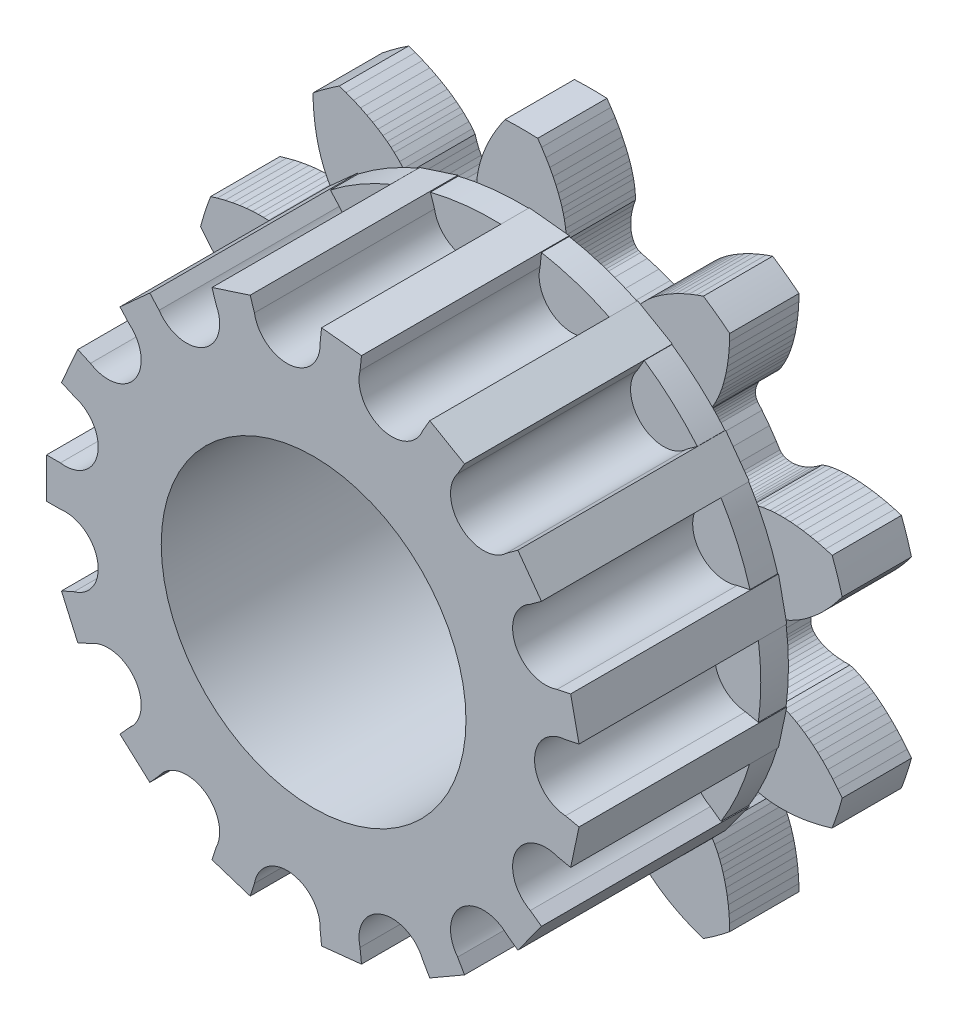
SolidWorks part; units mm, degrees
ref_plane "Front Plane" through (0, 0, 0) normal (0, 0, 1) x (1, 0, 0)
ref_plane "Top Plane" through (0, 0, 0) normal (0, 1, 0) x (1, 0, 0)
ref_plane "Right Plane" through (0, 0, 0) normal (1, 0, 0) x (0, 0, -1)
sketch "Model" plane through (0, 0, 0) normal (0, 0, 1) x (1, 0, 0)
  line L0 (44.9714, -18.1936) -> (45.0072, -17.6135)
  line L1 (45.0072, -17.6135) -> (45.064, -17.0676)
  line L2 (45.064, -17.0676) -> (45.1386, -16.5586)
  line L3 (45.1386, -16.5586) -> (45.2286, -16.0837)
  line L4 (45.2286, -16.0837) -> (45.3307, -15.6464)
  line L5 (45.3307, -15.6464) -> (45.4422, -15.245)
  line L6 (45.4422, -15.245) -> (45.5601, -14.8808)
  line L7 (45.5601, -14.8808) -> (45.6817, -14.5526)
  line L8 (45.6817, -14.5526) -> (45.8046, -14.2592)
  line L9 (45.8046, -14.2592) -> (46.0415, -13.7787)
  line L10 (46.0415, -13.7787) -> (46.2493, -13.433)
  line L11 (46.2493, -13.433) -> (46.4387, -13.1745)
  line L12 (46.4387, -13.1745) -> (46.7566, -12.9496)
  line L13 (46.7566, -12.9496) -> (47.0768, -12.6883)
  line L14 (47.0768, -12.6883) -> (47.3522, -12.4243)
  line L15 (47.3522, -12.4243) -> (47.5834, -12.1609)
  line L16 (47.5834, -12.1609) -> (47.7708, -11.9014)
  line L17 (47.7708, -11.9014) -> (47.9153, -11.6488)
  line L18 (47.9153, -11.6488) -> (48.0178, -11.4063)
  line L19 (48.0178, -11.4063) -> (48.0795, -11.177)
  line L20 (48.0795, -11.177) -> (48.1017, -10.9637)
  line L21 (48.1017, -10.9637) -> (48.086, -10.7695)
  line L22 (48.086, -10.7695) -> (48.034, -10.597)
  line L23 (48.034, -10.597) -> (47.9475, -10.4489)
  line L24 (47.9475, -10.4489) -> (47.6302, -10.0694)
  line L25 (47.6302, -10.0694) -> (47.0962, -9.3752)
  line L26 (47.0962, -9.3752) -> (46.601, -8.6528)
  line L27 (46.601, -8.6528) -> (46.3381, -8.2337)
  line L28 (46.3381, -8.2337) -> (46.224, -8.1057)
  line L29 (46.224, -8.1057) -> (46.076, -8.0029)
  line L30 (46.076, -8.0029) -> (45.8961, -7.9279)
  line L31 (45.8961, -7.9279) -> (45.6864, -7.8832)
  line L32 (45.6864, -7.8832) -> (45.4493, -7.871)
  line L33 (45.4493, -7.871) -> (45.187, -7.8936)
  line L34 (45.187, -7.8936) -> (44.9021, -7.9529)
  line L35 (44.9021, -7.9529) -> (44.5973, -8.051)
  line L36 (44.5973, -8.051) -> (44.2754, -8.1894)
  line L37 (44.2754, -8.1894) -> (43.9392, -8.3698)
  line L38 (43.9392, -8.3698) -> (43.5918, -8.5936)
  line L39 (43.5918, -8.5936) -> (43.2796, -8.8264)
  line L40 (43.2796, -8.8264) -> (42.9752, -8.9266)
  line L41 (42.9752, -8.9266) -> (42.5822, -9.0175)
  line L42 (42.5822, -9.0175) -> (42.052, -9.0943)
  line L43 (42.052, -9.0943) -> (41.735, -9.1205)
  line L44 (41.735, -9.1205) -> (41.3854, -9.1348)
  line L45 (41.3854, -9.1348) -> (41.0026, -9.1343)
  line L46 (41.0026, -9.1343) -> (40.5863, -9.1164)
  line L47 (40.5863, -9.1164) -> (40.1389, -9.0783)
  line L48 (40.1389, -9.0783) -> (39.6594, -9.0172)
  line L49 (39.6594, -9.0172) -> (39.1523, -8.9308)
  line L50 (39.1523, -8.9308) -> (38.6155, -8.8161)
  line L51 (38.6155, -8.8161) -> (38.0528, -8.671)
  line L52 (38.0528, -8.671) -> (37.565, -8.5243)
  line L53 (36.8392, -6.2906) -> (37.1476, -5.8853)
  line L54 (37.1476, -5.8853) -> (37.5176, -5.4371)
  line L55 (37.5176, -5.4371) -> (37.8845, -5.0288)
  line L56 (37.8845, -5.0288) -> (38.244, -4.6608)
  line L57 (38.244, -4.6608) -> (38.596, -4.3295)
  line L58 (38.596, -4.3295) -> (38.9355, -4.0358)
  line L59 (38.9355, -4.0358) -> (39.2618, -3.7766)
  line L60 (39.2618, -3.7766) -> (39.5712, -3.5512)
  line L61 (39.5712, -3.5512) -> (39.8624, -3.3572)
  line L62 (39.8624, -3.3572) -> (40.1343, -3.1921)
  line L63 (40.1343, -3.1921) -> (40.6084, -2.9426)
  line L64 (40.6084, -2.9426) -> (40.9797, -2.7851)
  line L65 (40.9797, -2.7851) -> (41.2849, -2.6873)
  line L66 (41.2849, -2.6873) -> (41.6743, -2.6921)
  line L67 (41.6743, -2.6921) -> (42.0869, -2.669)
  line L68 (42.0869, -2.669) -> (42.4649, -2.6173)
  line L69 (42.4649, -2.6173) -> (42.8067, -2.5401)
  line L70 (42.8067, -2.5401) -> (43.1109, -2.4403)
  line L71 (43.1109, -2.4403) -> (43.3763, -2.3209)
  line L72 (43.3763, -2.3209) -> (43.6018, -2.1849)
  line L73 (43.6018, -2.1849) -> (43.7865, -2.0357)
  line L74 (43.7865, -2.0357) -> (43.9298, -1.8762)
  line L75 (43.9298, -1.8762) -> (44.0312, -1.7098)
  line L76 (44.0312, -1.7098) -> (44.0905, -1.5397)
  line L77 (44.0905, -1.5397) -> (44.1076, -1.369)
  line L78 (44.1076, -1.369) -> (44.074, -0.8755)
  line L79 (44.074, -0.8755) -> (44.05, 0)
  line L80 (44.05, 0) -> (44.074, 0.8755)
  line L81 (44.074, 0.8755) -> (44.1076, 1.369)
  line L82 (44.1076, 1.369) -> (44.0905, 1.5397)
  line L83 (44.0905, 1.5397) -> (44.0312, 1.7098)
  line L84 (44.0312, 1.7098) -> (43.9298, 1.8762)
  line L85 (43.9298, 1.8762) -> (43.7865, 2.0357)
  line L86 (43.7865, 2.0357) -> (43.6018, 2.1849)
  line L87 (43.6018, 2.1849) -> (43.3763, 2.3209)
  line L88 (43.3763, 2.3209) -> (43.1109, 2.4403)
  line L89 (43.1109, 2.4403) -> (42.8067, 2.5401)
  line L90 (42.8067, 2.5401) -> (42.4649, 2.6173)
  line L91 (42.4649, 2.6173) -> (42.0869, 2.669)
  line L92 (42.0869, 2.669) -> (41.6743, 2.6921)
  line L93 (41.6743, 2.6921) -> (41.2849, 2.6873)
  line L94 (41.2849, 2.6873) -> (40.9797, 2.7851)
  line L95 (40.9797, 2.7851) -> (40.6084, 2.9426)
  line L96 (40.6084, 2.9426) -> (40.1343, 3.1921)
  line L97 (40.1343, 3.1921) -> (39.8624, 3.3572)
  line L98 (39.8624, 3.3572) -> (39.5712, 3.5512)
  line L99 (39.5712, 3.5512) -> (39.2618, 3.7766)
  line L100 (39.2618, 3.7766) -> (38.9355, 4.0358)
  line L101 (38.9355, 4.0358) -> (38.596, 4.3295)
  line L102 (38.596, 4.3295) -> (38.244, 4.6608)
  line L103 (38.244, 4.6608) -> (37.8845, 5.0288)
  line L104 (37.8845, 5.0288) -> (37.5176, 5.4371)
  line L105 (37.5176, 5.4371) -> (37.1476, 5.8853)
  line L106 (37.1476, 5.8853) -> (36.8392, 6.2906)
  line L107 (37.565, 8.5243) -> (38.0528, 8.671)
  line L108 (38.0528, 8.671) -> (38.6155, 8.8161)
  line L109 (38.6155, 8.8161) -> (39.1523, 8.9308)
  line L110 (39.1523, 8.9308) -> (39.6594, 9.0172)
  line L111 (39.6594, 9.0172) -> (40.1389, 9.0783)
  line L112 (40.1389, 9.0783) -> (40.5863, 9.1164)
  line L113 (40.5863, 9.1164) -> (41.0026, 9.1343)
  line L114 (41.0026, 9.1343) -> (41.3854, 9.1348)
  line L115 (41.3854, 9.1348) -> (41.735, 9.1205)
  line L116 (41.735, 9.1205) -> (42.052, 9.0943)
  line L117 (42.052, 9.0943) -> (42.5822, 9.0175)
  line L118 (42.5822, 9.0175) -> (42.9752, 8.9266)
  line L119 (42.9752, 8.9266) -> (43.2796, 8.8264)
  line L120 (43.2796, 8.8264) -> (43.5918, 8.5936)
  line L121 (43.5918, 8.5936) -> (43.9392, 8.3698)
  line L122 (43.9392, 8.3698) -> (44.2754, 8.1894)
  line L123 (44.2754, 8.1894) -> (44.5973, 8.051)
  line L124 (44.5973, 8.051) -> (44.9021, 7.9529)
  line L125 (44.9021, 7.9529) -> (45.187, 7.8936)
  line L126 (45.187, 7.8936) -> (45.4493, 7.871)
  line L127 (45.4493, 7.871) -> (45.6864, 7.8832)
  line L128 (45.6864, 7.8832) -> (45.8961, 7.9279)
  line L129 (45.8961, 7.9279) -> (46.076, 8.0029)
  line L130 (46.076, 8.0029) -> (46.224, 8.1057)
  line L131 (46.224, 8.1057) -> (46.3381, 8.2337)
  line L132 (46.3381, 8.2337) -> (46.601, 8.6528)
  line L133 (46.601, 8.6528) -> (47.0962, 9.3752)
  line L134 (47.0962, 9.3752) -> (47.6302, 10.0694)
  line L135 (47.6302, 10.0694) -> (47.9475, 10.4489)
  line L136 (47.9475, 10.4489) -> (48.034, 10.597)
  line L137 (48.034, 10.597) -> (48.086, 10.7695)
  line L138 (48.086, 10.7695) -> (48.1017, 10.9637)
  line L139 (48.1017, 10.9637) -> (48.0795, 11.177)
  line L140 (48.0795, 11.177) -> (48.0178, 11.4063)
  line L141 (48.0178, 11.4063) -> (47.9153, 11.6488)
  line L142 (47.9153, 11.6488) -> (47.7708, 11.9014)
  line L143 (47.7708, 11.9014) -> (47.5834, 12.1609)
  line L144 (47.5834, 12.1609) -> (47.3522, 12.4243)
  line L145 (47.3522, 12.4243) -> (47.0768, 12.6883)
  line L146 (47.0768, 12.6883) -> (46.7566, 12.9496)
  line L147 (46.7566, 12.9496) -> (46.4387, 13.1745)
  line L148 (46.4387, 13.1745) -> (46.2493, 13.433)
  line L149 (46.2493, 13.433) -> (46.0415, 13.7787)
  line L150 (46.0415, 13.7787) -> (45.8046, 14.2592)
  line L151 (45.8046, 14.2592) -> (45.6817, 14.5526)
  line L152 (45.6817, 14.5526) -> (45.5601, 14.8808)
  line L153 (45.5601, 14.8808) -> (45.4422, 15.245)
  line L154 (45.4422, 15.245) -> (45.3307, 15.6464)
  line L155 (45.3307, 15.6464) -> (45.2286, 16.0837)
  line L156 (45.2286, 16.0837) -> (45.1386, 16.5586)
  line L157 (45.1386, 16.5586) -> (45.064, 17.0676)
  line L158 (45.064, 17.0676) -> (45.0072, 17.6135)
  line L159 (45.0072, 17.6135) -> (44.9714, 18.1936)
  line L160 (44.9714, 18.1936) -> (44.9601, 18.7028)
  line L161 (46.8602, 20.0833) -> (47.341, 19.9152)
  line L162 (47.341, 19.9152) -> (47.8816, 19.7019)
  line L163 (47.8816, 19.7019) -> (48.3833, 19.4792)
  line L164 (48.3833, 19.4792) -> (48.8443, 19.2509)
  line L165 (48.8443, 19.2509) -> (49.2681, 19.0186)
  line L166 (49.2681, 19.0186) -> (49.6525, 18.7864)
  line L167 (49.6525, 18.7864) -> (49.9998, 18.5562)
  line L168 (49.9998, 18.5562) -> (50.3097, 18.3316)
  line L169 (50.3097, 18.3316) -> (50.5842, 18.1146)
  line L170 (50.5842, 18.1146) -> (50.8253, 17.907)
  line L171 (50.8253, 17.907) -> (51.2091, 17.5332)
  line L172 (51.2091, 17.5332) -> (51.4736, 17.2287)
  line L173 (51.4736, 17.2287) -> (51.6609, 16.9687)
  line L174 (51.6609, 16.9687) -> (51.7767, 16.5968)
  line L175 (51.7767, 16.5968) -> (51.9262, 16.2116)
  line L176 (51.9262, 16.2116) -> (52.0921, 15.8681)
  line L177 (52.0921, 15.8681) -> (52.2712, 15.5668)
  line L178 (52.2712, 15.5668) -> (52.4601, 15.3084)
  line L179 (52.4601, 15.3084) -> (52.6557, 15.0929)
  line L180 (52.6557, 15.0929) -> (52.8547, 14.9205)
  line L181 (52.8547, 14.9205) -> (53.0537, 14.7909)
  line L182 (53.0537, 14.7909) -> (53.2496, 14.7039)
  line L183 (53.2496, 14.7039) -> (53.4392, 14.6588)
  line L184 (53.4392, 14.6588) -> (53.6194, 14.655)
  line L185 (53.6194, 14.655) -> (53.7869, 14.6915)
  line L186 (53.7869, 14.6915) -> (54.2459, 14.876)
  line L187 (54.2459, 14.876) -> (55.0712, 15.1694)
  line L188 (55.0712, 15.1694) -> (55.9113, 15.4171)
  line L189 (55.9113, 15.4171) -> (56.391, 15.5376)
  line L190 (56.391, 15.5376) -> (56.548, 15.6066)
  line L191 (56.548, 15.6066) -> (56.6915, 15.7156)
  line L192 (56.6915, 15.7156) -> (56.8184, 15.8635)
  line L193 (56.8184, 15.8635) -> (56.9258, 16.049)
  line L194 (56.9258, 16.049) -> (57.0107, 16.2708)
  line L195 (57.0107, 16.2708) -> (57.0703, 16.5273)
  line L196 (57.0703, 16.5273) -> (57.1018, 16.8165)
  line L197 (57.1018, 16.8165) -> (57.1028, 17.1367)
  line L198 (57.1028, 17.1367) -> (57.0706, 17.4857)
  line L199 (57.0706, 17.4857) -> (57.0029, 17.8611)
  line L200 (57.0029, 17.8611) -> (56.8974, 18.2607)
  line L201 (56.8974, 18.2607) -> (56.7725, 18.6296)
  line L202 (56.7725, 18.6296) -> (56.7712, 18.95)
  line L203 (56.7712, 18.95) -> (56.8063, 19.3518)
  line L204 (56.8063, 19.3518) -> (56.897, 19.8798)
  line L205 (56.897, 19.8798) -> (56.97, 20.1894)
  line L206 (56.97, 20.1894) -> (57.0646, 20.5264)
  line L207 (57.0646, 20.5264) -> (57.1833, 20.8903)
  line L208 (57.1833, 20.8903) -> (57.329, 21.2806)
  line L209 (57.329, 21.2806) -> (57.5034, 21.6944)
  line L210 (57.5034, 21.6944) -> (57.7097, 22.1315)
  line L211 (57.7097, 22.1315) -> (57.9486, 22.5871)
  line L212 (57.9486, 22.5871) -> (58.2236, 23.0622)
  line L213 (58.2236, 23.0622) -> (58.5355, 23.5525)
  line L214 (58.5355, 23.5525) -> (58.8257, 23.9711)
  line L215 (61.1743, 23.9711) -> (61.4645, 23.5525)
  line L216 (61.4645, 23.5525) -> (61.7764, 23.0622)
  line L217 (61.7764, 23.0622) -> (62.0514, 22.5871)
  line L218 (62.0514, 22.5871) -> (62.2903, 22.1315)
  line L219 (62.2903, 22.1315) -> (62.4966, 21.6944)
  line L220 (62.4966, 21.6944) -> (62.671, 21.2806)
  line L221 (62.671, 21.2806) -> (62.8167, 20.8903)
  line L222 (62.8167, 20.8903) -> (62.9354, 20.5264)
  line L223 (62.9354, 20.5264) -> (63.03, 20.1894)
  line L224 (63.03, 20.1894) -> (63.103, 19.8798)
  line L225 (63.103, 19.8798) -> (63.1937, 19.3518)
  line L226 (63.1937, 19.3518) -> (63.2288, 18.95)
  line L227 (63.2288, 18.95) -> (63.2275, 18.6296)
  line L228 (63.2275, 18.6296) -> (63.1026, 18.2607)
  line L229 (63.1026, 18.2607) -> (62.9971, 17.8611)
  line L230 (62.9971, 17.8611) -> (62.9294, 17.4857)
  line L231 (62.9294, 17.4857) -> (62.8972, 17.1367)
  line L232 (62.8972, 17.1367) -> (62.8982, 16.8165)
  line L233 (62.8982, 16.8165) -> (62.9297, 16.5273)
  line L234 (62.9297, 16.5273) -> (62.9893, 16.2708)
  line L235 (62.9893, 16.2708) -> (63.0742, 16.049)
  line L236 (63.0742, 16.049) -> (63.1816, 15.8635)
  line L237 (63.1816, 15.8635) -> (63.3085, 15.7156)
  line L238 (63.3085, 15.7156) -> (63.452, 15.6066)
  line L239 (63.452, 15.6066) -> (63.609, 15.5376)
  line L240 (63.609, 15.5376) -> (64.0887, 15.4171)
  line L241 (64.0887, 15.4171) -> (64.9288, 15.1694)
  line L242 (64.9288, 15.1694) -> (65.7541, 14.876)
  line L243 (65.7541, 14.876) -> (66.2131, 14.6915)
  line L244 (66.2131, 14.6915) -> (66.3806, 14.655)
  line L245 (66.3806, 14.655) -> (66.5608, 14.6588)
  line L246 (66.5608, 14.6588) -> (66.7504, 14.7039)
  line L247 (66.7504, 14.7039) -> (66.9463, 14.7909)
  line L248 (66.9463, 14.7909) -> (67.1453, 14.9205)
  line L249 (67.1453, 14.9205) -> (67.3443, 15.0929)
  line L250 (67.3443, 15.0929) -> (67.5399, 15.3084)
  line L251 (67.5399, 15.3084) -> (67.7288, 15.5668)
  line L252 (67.7288, 15.5668) -> (67.9079, 15.8681)
  line L253 (67.9079, 15.8681) -> (68.0738, 16.2116)
  line L254 (68.0738, 16.2116) -> (68.2233, 16.5968)
  line L255 (68.2233, 16.5968) -> (68.3391, 16.9687)
  line L256 (68.3391, 16.9687) -> (68.5264, 17.2287)
  line L257 (68.5264, 17.2287) -> (68.7909, 17.5332)
  line L258 (68.7909, 17.5332) -> (69.1747, 17.907)
  line L259 (69.1747, 17.907) -> (69.4158, 18.1146)
  line L260 (69.4158, 18.1146) -> (69.6903, 18.3316)
  line L261 (69.6903, 18.3316) -> (70.0002, 18.5562)
  line L262 (70.0002, 18.5562) -> (70.3475, 18.7864)
  line L263 (70.3475, 18.7864) -> (70.7319, 19.0186)
  line L264 (70.7319, 19.0186) -> (71.1557, 19.2509)
  line L265 (71.1557, 19.2509) -> (71.6167, 19.4792)
  line L266 (71.6167, 19.4792) -> (72.1184, 19.7019)
  line L267 (72.1184, 19.7019) -> (72.659, 19.9152)
  line L268 (72.659, 19.9152) -> (73.1398, 20.0833)
  line L269 (75.0399, 18.7028) -> (75.0286, 18.1936)
  line L270 (75.0286, 18.1936) -> (74.9928, 17.6135)
  line L271 (74.9928, 17.6135) -> (74.936, 17.0676)
  line L272 (74.936, 17.0676) -> (74.8614, 16.5586)
  line L273 (74.8614, 16.5586) -> (74.7714, 16.0837)
  line L274 (74.7714, 16.0837) -> (74.6693, 15.6464)
  line L275 (74.6693, 15.6464) -> (74.5578, 15.245)
  line L276 (74.5578, 15.245) -> (74.4399, 14.8808)
  line L277 (74.4399, 14.8808) -> (74.3183, 14.5526)
  line L278 (74.3183, 14.5526) -> (74.1954, 14.2592)
  line L279 (74.1954, 14.2592) -> (73.9585, 13.7787)
  line L280 (73.9585, 13.7787) -> (73.7507, 13.433)
  line L281 (73.7507, 13.433) -> (73.5613, 13.1745)
  line L282 (73.5613, 13.1745) -> (73.2434, 12.9496)
  line L283 (73.2434, 12.9496) -> (72.9232, 12.6883)
  line L284 (72.9232, 12.6883) -> (72.6478, 12.4243)
  line L285 (72.6478, 12.4243) -> (72.4166, 12.1609)
  line L286 (72.4166, 12.1609) -> (72.2292, 11.9014)
  line L287 (72.2292, 11.9014) -> (72.0847, 11.6488)
  line L288 (72.0847, 11.6488) -> (71.9822, 11.4063)
  line L289 (71.9822, 11.4063) -> (71.9205, 11.177)
  line L290 (71.9205, 11.177) -> (71.8983, 10.9637)
  line L291 (71.8983, 10.9637) -> (71.914, 10.7695)
  line L292 (71.914, 10.7695) -> (71.966, 10.597)
  line L293 (71.966, 10.597) -> (72.0525, 10.4489)
  line L294 (72.0525, 10.4489) -> (72.3698, 10.0694)
  line L295 (72.3698, 10.0694) -> (72.9038, 9.3752)
  line L296 (72.9038, 9.3752) -> (73.399, 8.6528)
  line L297 (73.399, 8.6528) -> (73.6619, 8.2337)
  line L298 (73.6619, 8.2337) -> (73.776, 8.1057)
  line L299 (73.776, 8.1057) -> (73.924, 8.0029)
  line L300 (73.924, 8.0029) -> (74.1039, 7.9279)
  line L301 (74.1039, 7.9279) -> (74.3136, 7.8832)
  line L302 (74.3136, 7.8832) -> (74.5507, 7.871)
  line L303 (74.5507, 7.871) -> (74.813, 7.8936)
  line L304 (74.813, 7.8936) -> (75.0979, 7.9529)
  line L305 (75.0979, 7.9529) -> (75.4027, 8.051)
  line L306 (75.4027, 8.051) -> (75.7246, 8.1894)
  line L307 (75.7246, 8.1894) -> (76.0608, 8.3698)
  line L308 (76.0608, 8.3698) -> (76.4082, 8.5936)
  line L309 (76.4082, 8.5936) -> (76.7204, 8.8264)
  line L310 (76.7204, 8.8264) -> (77.0248, 8.9266)
  line L311 (77.0248, 8.9266) -> (77.4178, 9.0175)
  line L312 (77.4178, 9.0175) -> (77.948, 9.0943)
  line L313 (77.948, 9.0943) -> (78.265, 9.1205)
  line L314 (78.265, 9.1205) -> (78.6146, 9.1348)
  line L315 (78.6146, 9.1348) -> (78.9974, 9.1343)
  line L316 (78.9974, 9.1343) -> (79.4137, 9.1164)
  line L317 (79.4137, 9.1164) -> (79.8611, 9.0783)
  line L318 (79.8611, 9.0783) -> (80.3406, 9.0172)
  line L319 (80.3406, 9.0172) -> (80.8477, 8.9308)
  line L320 (80.8477, 8.9308) -> (81.3845, 8.8161)
  line L321 (81.3845, 8.8161) -> (81.9472, 8.671)
  line L322 (81.9472, 8.671) -> (82.435, 8.5243)
  line L323 (83.1608, 6.2906) -> (82.8524, 5.8853)
  line L324 (82.8524, 5.8853) -> (82.4824, 5.4371)
  line L325 (82.4824, 5.4371) -> (82.1155, 5.0288)
  line L326 (82.1155, 5.0288) -> (81.756, 4.6608)
  line L327 (81.756, 4.6608) -> (81.4041, 4.3295)
  line L328 (81.4041, 4.3295) -> (81.0645, 4.0358)
  line L329 (81.0645, 4.0358) -> (80.7382, 3.7766)
  line L330 (80.7382, 3.7766) -> (80.4288, 3.5512)
  line L331 (80.4288, 3.5512) -> (80.1376, 3.3572)
  line L332 (80.1376, 3.3572) -> (79.8657, 3.1921)
  line L333 (79.8657, 3.1921) -> (79.3916, 2.9426)
  line L334 (79.3916, 2.9426) -> (79.0203, 2.7851)
  line L335 (79.0203, 2.7851) -> (78.7151, 2.6873)
  line L336 (78.7151, 2.6873) -> (78.3257, 2.6921)
  line L337 (78.3257, 2.6921) -> (77.9131, 2.669)
  line L338 (77.9131, 2.669) -> (77.5351, 2.6173)
  line L339 (77.5351, 2.6173) -> (77.1933, 2.5401)
  line L340 (77.1933, 2.5401) -> (76.8891, 2.4403)
  line L341 (76.8891, 2.4403) -> (76.6237, 2.3209)
  line L342 (76.6237, 2.3209) -> (76.3983, 2.1849)
  line L343 (76.3983, 2.1849) -> (76.2135, 2.0357)
  line L344 (76.2135, 2.0357) -> (76.0702, 1.8762)
  line L345 (76.0702, 1.8762) -> (75.9688, 1.7098)
  line L346 (75.9688, 1.7098) -> (75.9095, 1.5397)
  line L347 (75.9095, 1.5397) -> (75.8924, 1.369)
  line L348 (75.8924, 1.369) -> (75.926, 0.8755)
  line L349 (75.926, 0.8755) -> (75.95, 0)
  line L350 (75.95, 0) -> (75.926, -0.8755)
  line L351 (75.926, -0.8755) -> (75.8924, -1.369)
  line L352 (75.8924, -1.369) -> (75.9095, -1.5397)
  line L353 (75.9095, -1.5397) -> (75.9688, -1.7098)
  line L354 (75.9688, -1.7098) -> (76.0702, -1.8762)
  line L355 (76.0702, -1.8762) -> (76.2135, -2.0357)
  line L356 (76.2135, -2.0357) -> (76.3983, -2.1849)
  line L357 (76.3983, -2.1849) -> (76.6237, -2.3209)
  line L358 (76.6237, -2.3209) -> (76.8891, -2.4403)
  line L359 (76.8891, -2.4403) -> (77.1933, -2.5401)
  line L360 (77.1933, -2.5401) -> (77.5351, -2.6173)
  line L361 (77.5351, -2.6173) -> (77.9131, -2.669)
  line L362 (77.9131, -2.669) -> (78.3257, -2.6921)
  line L363 (78.3257, -2.6921) -> (78.7151, -2.6873)
  line L364 (78.7151, -2.6873) -> (79.0203, -2.7851)
  line L365 (79.0203, -2.7851) -> (79.3916, -2.9426)
  line L366 (79.3916, -2.9426) -> (79.8657, -3.1921)
  line L367 (79.8657, -3.1921) -> (80.1376, -3.3572)
  line L368 (80.1376, -3.3572) -> (80.4288, -3.5512)
  line L369 (80.4288, -3.5512) -> (80.7382, -3.7766)
  line L370 (80.7382, -3.7766) -> (81.0645, -4.0358)
  line L371 (81.0645, -4.0358) -> (81.4041, -4.3295)
  line L372 (81.4041, -4.3295) -> (81.756, -4.6608)
  line L373 (81.756, -4.6608) -> (82.1155, -5.0288)
  line L374 (82.1155, -5.0288) -> (82.4824, -5.4371)
  line L375 (82.4824, -5.4371) -> (82.8524, -5.8853)
  line L376 (82.8524, -5.8853) -> (83.1608, -6.2906)
  line L377 (82.435, -8.5243) -> (81.9472, -8.671)
  line L378 (81.9472, -8.671) -> (81.3845, -8.8161)
  line L379 (81.3845, -8.8161) -> (80.8477, -8.9308)
  line L380 (80.8477, -8.9308) -> (80.3406, -9.0172)
  line L381 (80.3406, -9.0172) -> (79.8611, -9.0783)
  line L382 (79.8611, -9.0783) -> (79.4137, -9.1164)
  line L383 (79.4137, -9.1164) -> (78.9974, -9.1343)
  line L384 (78.9974, -9.1343) -> (78.6146, -9.1348)
  line L385 (78.6146, -9.1348) -> (78.265, -9.1205)
  line L386 (78.265, -9.1205) -> (77.948, -9.0943)
  line L387 (77.948, -9.0943) -> (77.4178, -9.0175)
  line L388 (77.4178, -9.0175) -> (77.0248, -8.9266)
  line L389 (77.0248, -8.9266) -> (76.7204, -8.8264)
  line L390 (76.7204, -8.8264) -> (76.4082, -8.5936)
  line L391 (76.4082, -8.5936) -> (76.0608, -8.3698)
  line L392 (76.0608, -8.3698) -> (75.7246, -8.1894)
  line L393 (75.7246, -8.1894) -> (75.4027, -8.051)
  line L394 (75.4027, -8.051) -> (75.0979, -7.9529)
  line L395 (75.0979, -7.9529) -> (74.813, -7.8936)
  line L396 (74.813, -7.8936) -> (74.5507, -7.871)
  line L397 (74.5507, -7.871) -> (74.3136, -7.8832)
  line L398 (74.3136, -7.8832) -> (74.1039, -7.9279)
  line L399 (74.1039, -7.9279) -> (73.924, -8.0029)
  line L400 (73.924, -8.0029) -> (73.776, -8.1057)
  line L401 (73.776, -8.1057) -> (73.6619, -8.2337)
  line L402 (73.6619, -8.2337) -> (73.399, -8.6528)
  line L403 (73.399, -8.6528) -> (72.9038, -9.3752)
  line L404 (72.9038, -9.3752) -> (72.3698, -10.0694)
  line L405 (72.3698, -10.0694) -> (72.0525, -10.4489)
  line L406 (72.0525, -10.4489) -> (71.966, -10.597)
  line L407 (71.966, -10.597) -> (71.914, -10.7695)
  line L408 (71.914, -10.7695) -> (71.8983, -10.9637)
  line L409 (71.8983, -10.9637) -> (71.9205, -11.177)
  line L410 (71.9205, -11.177) -> (71.9822, -11.4063)
  line L411 (71.9822, -11.4063) -> (72.0847, -11.6488)
  line L412 (72.0847, -11.6488) -> (72.2292, -11.9014)
  line L413 (72.2292, -11.9014) -> (72.4166, -12.1609)
  line L414 (72.4166, -12.1609) -> (72.6478, -12.4243)
  line L415 (72.6478, -12.4243) -> (72.9232, -12.6883)
  line L416 (72.9232, -12.6883) -> (73.2434, -12.9496)
  line L417 (73.2434, -12.9496) -> (73.5613, -13.1745)
  line L418 (73.5613, -13.1745) -> (73.7507, -13.433)
  line L419 (73.7507, -13.433) -> (73.9585, -13.7787)
  line L420 (73.9585, -13.7787) -> (74.1954, -14.2592)
  line L421 (74.1954, -14.2592) -> (74.3183, -14.5526)
  line L422 (74.3183, -14.5526) -> (74.4399, -14.8808)
  line L423 (74.4399, -14.8808) -> (74.5578, -15.245)
  line L424 (74.5578, -15.245) -> (74.6693, -15.6464)
  line L425 (74.6693, -15.6464) -> (74.7714, -16.0837)
  line L426 (74.7714, -16.0837) -> (74.8614, -16.5586)
  line L427 (74.8614, -16.5586) -> (74.936, -17.0676)
  line L428 (74.936, -17.0676) -> (74.9928, -17.6135)
  line L429 (74.9928, -17.6135) -> (75.0286, -18.1936)
  line L430 (75.0286, -18.1936) -> (75.0399, -18.7028)
  line L431 (73.1398, -20.0833) -> (72.659, -19.9152)
  line L432 (72.659, -19.9152) -> (72.1184, -19.7019)
  line L433 (72.1184, -19.7019) -> (71.6167, -19.4792)
  line L434 (71.6167, -19.4792) -> (71.1557, -19.2509)
  line L435 (71.1557, -19.2509) -> (70.7319, -19.0186)
  line L436 (70.7319, -19.0186) -> (70.3475, -18.7864)
  line L437 (70.3475, -18.7864) -> (70.0002, -18.5562)
  line L438 (70.0002, -18.5562) -> (69.6903, -18.3316)
  line L439 (69.6903, -18.3316) -> (69.4158, -18.1146)
  line L440 (69.4158, -18.1146) -> (69.1747, -17.907)
  line L441 (69.1747, -17.907) -> (68.7909, -17.5332)
  line L442 (68.7909, -17.5332) -> (68.5264, -17.2287)
  line L443 (68.5264, -17.2287) -> (68.3391, -16.9687)
  line L444 (68.3391, -16.9687) -> (68.2233, -16.5968)
  line L445 (68.2233, -16.5968) -> (68.0738, -16.2116)
  line L446 (68.0738, -16.2116) -> (67.9079, -15.8681)
  line L447 (67.9079, -15.8681) -> (67.7288, -15.5668)
  line L448 (67.7288, -15.5668) -> (67.5399, -15.3084)
  line L449 (67.5399, -15.3084) -> (67.3443, -15.0929)
  line L450 (67.3443, -15.0929) -> (67.1453, -14.9205)
  line L451 (67.1453, -14.9205) -> (66.9463, -14.7909)
  line L452 (66.9463, -14.7909) -> (66.7504, -14.7039)
  line L453 (66.7504, -14.7039) -> (66.5608, -14.6588)
  line L454 (66.5608, -14.6588) -> (66.3806, -14.655)
  line L455 (66.3806, -14.655) -> (66.2131, -14.6915)
  line L456 (66.2131, -14.6915) -> (65.7541, -14.876)
  line L457 (65.7541, -14.876) -> (64.9288, -15.1694)
  line L458 (64.9288, -15.1694) -> (64.0887, -15.4171)
  line L459 (64.0887, -15.4171) -> (63.609, -15.5376)
  line L460 (63.609, -15.5376) -> (63.452, -15.6066)
  line L461 (63.452, -15.6066) -> (63.3085, -15.7156)
  line L462 (63.3085, -15.7156) -> (63.1816, -15.8635)
  line L463 (63.1816, -15.8635) -> (63.0742, -16.049)
  line L464 (63.0742, -16.049) -> (62.9893, -16.2708)
  line L465 (62.9893, -16.2708) -> (62.9297, -16.5273)
  line L466 (62.9297, -16.5273) -> (62.8982, -16.8165)
  line L467 (62.8982, -16.8165) -> (62.8972, -17.1367)
  line L468 (62.8972, -17.1367) -> (62.9294, -17.4857)
  line L469 (62.9294, -17.4857) -> (62.9971, -17.8611)
  line L470 (62.9971, -17.8611) -> (63.1026, -18.2607)
  line L471 (63.1026, -18.2607) -> (63.2275, -18.6296)
  line L472 (63.2275, -18.6296) -> (63.2288, -18.95)
  line L473 (63.2288, -18.95) -> (63.1937, -19.3518)
  line L474 (63.1937, -19.3518) -> (63.103, -19.8798)
  line L475 (63.103, -19.8798) -> (63.03, -20.1894)
  line L476 (63.03, -20.1894) -> (62.9354, -20.5264)
  line L477 (62.9354, -20.5264) -> (62.8167, -20.8903)
  line L478 (62.8167, -20.8903) -> (62.671, -21.2806)
  line L479 (62.671, -21.2806) -> (62.4966, -21.6944)
  line L480 (62.4966, -21.6944) -> (62.2903, -22.1315)
  line L481 (62.2903, -22.1315) -> (62.0514, -22.5871)
  line L482 (62.0514, -22.5871) -> (61.7764, -23.0622)
  line L483 (61.7764, -23.0622) -> (61.4645, -23.5525)
  line L484 (61.4645, -23.5525) -> (61.1743, -23.9711)
  line L485 (58.8257, -23.9711) -> (58.5355, -23.5525)
  line L486 (58.5355, -23.5525) -> (58.2236, -23.0622)
  line L487 (58.2236, -23.0622) -> (57.9486, -22.5871)
  line L488 (57.9486, -22.5871) -> (57.7097, -22.1315)
  line L489 (57.7097, -22.1315) -> (57.5034, -21.6944)
  line L490 (57.5034, -21.6944) -> (57.329, -21.2806)
  line L491 (57.329, -21.2806) -> (57.1833, -20.8903)
  line L492 (57.1833, -20.8903) -> (57.0646, -20.5264)
  line L493 (57.0646, -20.5264) -> (56.97, -20.1894)
  line L494 (56.97, -20.1894) -> (56.897, -19.8798)
  line L495 (56.897, -19.8798) -> (56.8063, -19.3518)
  line L496 (56.8063, -19.3518) -> (56.7712, -18.95)
  line L497 (56.7712, -18.95) -> (56.7725, -18.6296)
  line L498 (56.7725, -18.6296) -> (56.8974, -18.2607)
  line L499 (56.8974, -18.2607) -> (57.0029, -17.8611)
  line L500 (57.0029, -17.8611) -> (57.0706, -17.4857)
  line L501 (57.0706, -17.4857) -> (57.1028, -17.1367)
  line L502 (57.1028, -17.1367) -> (57.1018, -16.8165)
  line L503 (57.1018, -16.8165) -> (57.0703, -16.5273)
  line L504 (57.0703, -16.5273) -> (57.0107, -16.2708)
  line L505 (57.0107, -16.2708) -> (56.9258, -16.049)
  line L506 (56.9258, -16.049) -> (56.8184, -15.8635)
  line L507 (56.8184, -15.8635) -> (56.6915, -15.7156)
  line L508 (56.6915, -15.7156) -> (56.548, -15.6066)
  line L509 (56.548, -15.6066) -> (56.391, -15.5376)
  line L510 (56.391, -15.5376) -> (55.9113, -15.4171)
  line L511 (55.9113, -15.4171) -> (55.0712, -15.1694)
  line L512 (55.0712, -15.1694) -> (54.2459, -14.876)
  line L513 (54.2459, -14.876) -> (53.7869, -14.6915)
  line L514 (53.7869, -14.6915) -> (53.6194, -14.655)
  line L515 (53.6194, -14.655) -> (53.4392, -14.6588)
  line L516 (53.4392, -14.6588) -> (53.2496, -14.7039)
  line L517 (53.2496, -14.7039) -> (53.0537, -14.7909)
  line L518 (53.0537, -14.7909) -> (52.8547, -14.9205)
  line L519 (52.8547, -14.9205) -> (52.6557, -15.0929)
  line L520 (52.6557, -15.0929) -> (52.4601, -15.3084)
  line L521 (52.4601, -15.3084) -> (52.2712, -15.5668)
  line L522 (52.2712, -15.5668) -> (52.0921, -15.8681)
  line L523 (52.0921, -15.8681) -> (51.9262, -16.2116)
  line L524 (51.9262, -16.2116) -> (51.7767, -16.5968)
  line L525 (51.7767, -16.5968) -> (51.6609, -16.9687)
  line L526 (51.6609, -16.9687) -> (51.4736, -17.2287)
  line L527 (51.4736, -17.2287) -> (51.2091, -17.5332)
  line L528 (51.2091, -17.5332) -> (50.8253, -17.907)
  line L529 (50.8253, -17.907) -> (50.5842, -18.1146)
  line L530 (50.5842, -18.1146) -> (50.3097, -18.3316)
  line L531 (50.3097, -18.3316) -> (49.9998, -18.5562)
  line L532 (49.9998, -18.5562) -> (49.6525, -18.7864)
  line L533 (49.6525, -18.7864) -> (49.2681, -19.0186)
  line L534 (49.2681, -19.0186) -> (48.8443, -19.2509)
  line L535 (48.8443, -19.2509) -> (48.3833, -19.4792)
  line L536 (48.3833, -19.4792) -> (47.8816, -19.7019)
  line L537 (47.8816, -19.7019) -> (47.341, -19.9152)
  line L538 (47.341, -19.9152) -> (46.8602, -20.0833)
  line L539 (44.9601, -18.7028) -> (44.9714, -18.1936)
  line L540 (44.9714, -18.1936) -> (45.0072, -17.6135)
  line L541 (45.0072, -17.6135) -> (45.064, -17.0676)
  line L542 (45.064, -17.0676) -> (45.1386, -16.5586)
  line L543 (45.1386, -16.5586) -> (45.2286, -16.0837)
  line L544 (45.2286, -16.0837) -> (45.3307, -15.6464)
  line L545 (45.3307, -15.6464) -> (45.4422, -15.245)
  line L546 (45.4422, -15.245) -> (45.5601, -14.8808)
  line L547 (45.5601, -14.8808) -> (45.6817, -14.5526)
  line L548 (45.6817, -14.5526) -> (45.8046, -14.2592)
  line L549 (45.8046, -14.2592) -> (46.0415, -13.7787)
  line L550 (46.0415, -13.7787) -> (46.2493, -13.433)
  line L551 (46.2493, -13.433) -> (46.4387, -13.1745)
  line L552 (46.4387, -13.1745) -> (46.7566, -12.9496)
  line L553 (46.7566, -12.9496) -> (47.0768, -12.6883)
  line L554 (47.0768, -12.6883) -> (47.3522, -12.4243)
  line L555 (47.3522, -12.4243) -> (47.5834, -12.1609)
  line L556 (47.5834, -12.1609) -> (47.7708, -11.9014)
  line L557 (47.7708, -11.9014) -> (47.9153, -11.6488)
  line L558 (47.9153, -11.6488) -> (48.0178, -11.4063)
  line L559 (48.0178, -11.4063) -> (48.0795, -11.177)
  line L560 (48.0795, -11.177) -> (48.1017, -10.9637)
  line L561 (48.1017, -10.9637) -> (48.086, -10.7695)
  line L562 (48.086, -10.7695) -> (48.034, -10.597)
  line L563 (48.034, -10.597) -> (47.9475, -10.4489)
  line L564 (47.9475, -10.4489) -> (47.6302, -10.0694)
  line L565 (47.6302, -10.0694) -> (47.0962, -9.3752)
  line L566 (47.0962, -9.3752) -> (46.601, -8.6528)
  line L567 (46.601, -8.6528) -> (46.3381, -8.2337)
  line L568 (46.3381, -8.2337) -> (46.224, -8.1057)
  line L569 (46.224, -8.1057) -> (46.076, -8.0029)
  line L570 (46.076, -8.0029) -> (45.8961, -7.9279)
  line L571 (45.8961, -7.9279) -> (45.6864, -7.8832)
  line L572 (45.6864, -7.8832) -> (45.4493, -7.871)
  line L573 (45.4493, -7.871) -> (45.187, -7.8936)
  line L574 (45.187, -7.8936) -> (44.9021, -7.9529)
  line L575 (44.9021, -7.9529) -> (44.5973, -8.051)
  line L576 (44.5973, -8.051) -> (44.2754, -8.1894)
  line L577 (44.2754, -8.1894) -> (43.9392, -8.3698)
  line L578 (43.9392, -8.3698) -> (43.5918, -8.5936)
  line L579 (43.5918, -8.5936) -> (43.2796, -8.8264)
  line L580 (43.2796, -8.8264) -> (42.9752, -8.9266)
  line L581 (42.9752, -8.9266) -> (42.5822, -9.0175)
  line L582 (42.5822, -9.0175) -> (42.052, -9.0943)
  line L583 (42.052, -9.0943) -> (41.735, -9.1205)
  line L584 (41.735, -9.1205) -> (41.3854, -9.1348)
  line L585 (41.3854, -9.1348) -> (41.0026, -9.1343)
  line L586 (41.0026, -9.1343) -> (40.5863, -9.1164)
  line L587 (40.5863, -9.1164) -> (40.1389, -9.0783)
  line L588 (40.1389, -9.0783) -> (39.6594, -9.0172)
  line L589 (39.6594, -9.0172) -> (39.1523, -8.9308)
  line L590 (39.1523, -8.9308) -> (38.6155, -8.8161)
  line L591 (38.6155, -8.8161) -> (38.0528, -8.671)
  line L592 (38.0528, -8.671) -> (37.565, -8.5243)
  line L593 (36.8392, -6.2906) -> (37.1476, -5.8853)
  line L594 (37.1476, -5.8853) -> (37.5176, -5.4371)
  line L595 (37.5176, -5.4371) -> (37.8845, -5.0288)
  line L596 (37.8845, -5.0288) -> (38.244, -4.6608)
  line L597 (38.244, -4.6608) -> (38.596, -4.3295)
  line L598 (38.596, -4.3295) -> (38.9355, -4.0358)
  line L599 (38.9355, -4.0358) -> (39.2618, -3.7766)
  line L600 (39.2618, -3.7766) -> (39.5712, -3.5512)
  line L601 (39.5712, -3.5512) -> (39.8624, -3.3572)
  line L602 (39.8624, -3.3572) -> (40.1343, -3.1921)
  line L603 (40.1343, -3.1921) -> (40.6084, -2.9426)
  line L604 (40.6084, -2.9426) -> (40.9797, -2.7851)
  line L605 (40.9797, -2.7851) -> (41.2849, -2.6873)
  line L606 (41.2849, -2.6873) -> (41.6743, -2.6921)
  line L607 (41.6743, -2.6921) -> (42.0869, -2.669)
  line L608 (42.0869, -2.669) -> (42.4649, -2.6173)
  line L609 (42.4649, -2.6173) -> (42.8067, -2.5401)
  line L610 (42.8067, -2.5401) -> (43.1109, -2.4403)
  line L611 (43.1109, -2.4403) -> (43.3763, -2.3209)
  line L612 (43.3763, -2.3209) -> (43.6018, -2.1849)
  line L613 (43.6018, -2.1849) -> (43.7865, -2.0357)
  line L614 (43.7865, -2.0357) -> (43.9298, -1.8762)
  line L615 (43.9298, -1.8762) -> (44.0312, -1.7098)
  line L616 (44.0312, -1.7098) -> (44.0905, -1.5397)
  line L617 (44.0905, -1.5397) -> (44.1076, -1.369)
  line L618 (44.1076, -1.369) -> (44.074, -0.8755)
  line L619 (44.074, -0.8755) -> (44.05, 0)
  line L620 (44.05, 0) -> (44.074, 0.8755)
  line L621 (44.074, 0.8755) -> (44.1076, 1.369)
  line L622 (44.1076, 1.369) -> (44.0905, 1.5397)
  line L623 (44.0905, 1.5397) -> (44.0312, 1.7098)
  line L624 (44.0312, 1.7098) -> (43.9298, 1.8762)
  line L625 (43.9298, 1.8762) -> (43.7865, 2.0357)
  line L626 (43.7865, 2.0357) -> (43.6018, 2.1849)
  line L627 (43.6018, 2.1849) -> (43.3763, 2.3209)
  line L628 (43.3763, 2.3209) -> (43.1109, 2.4403)
  line L629 (43.1109, 2.4403) -> (42.8067, 2.5401)
  line L630 (42.8067, 2.5401) -> (42.4649, 2.6173)
  line L631 (42.4649, 2.6173) -> (42.0869, 2.669)
  line L632 (42.0869, 2.669) -> (41.6743, 2.6921)
  line L633 (41.6743, 2.6921) -> (41.2849, 2.6873)
  line L634 (41.2849, 2.6873) -> (40.9797, 2.7851)
  line L635 (40.9797, 2.7851) -> (40.6084, 2.9426)
  line L636 (40.6084, 2.9426) -> (40.1343, 3.1921)
  line L637 (40.1343, 3.1921) -> (39.8624, 3.3572)
  line L638 (39.8624, 3.3572) -> (39.5712, 3.5512)
  line L639 (39.5712, 3.5512) -> (39.2618, 3.7766)
  line L640 (39.2618, 3.7766) -> (38.9355, 4.0358)
  line L641 (38.9355, 4.0358) -> (38.596, 4.3295)
  line L642 (38.596, 4.3295) -> (38.244, 4.6608)
  line L643 (38.244, 4.6608) -> (37.8845, 5.0288)
  line L644 (37.8845, 5.0288) -> (37.5176, 5.4371)
  line L645 (37.5176, 5.4371) -> (37.1476, 5.8853)
  line L646 (37.1476, 5.8853) -> (36.8392, 6.2906)
  line L647 (37.565, 8.5243) -> (38.0528, 8.671)
  line L648 (38.0528, 8.671) -> (38.6155, 8.8161)
  line L649 (38.6155, 8.8161) -> (39.1523, 8.9308)
  line L650 (39.1523, 8.9308) -> (39.6594, 9.0172)
  line L651 (39.6594, 9.0172) -> (40.1389, 9.0783)
  line L652 (40.1389, 9.0783) -> (40.5863, 9.1164)
  line L653 (40.5863, 9.1164) -> (41.0026, 9.1343)
  line L654 (41.0026, 9.1343) -> (41.3854, 9.1348)
  line L655 (41.3854, 9.1348) -> (41.735, 9.1205)
  line L656 (41.735, 9.1205) -> (42.052, 9.0943)
  line L657 (42.052, 9.0943) -> (42.5822, 9.0175)
  line L658 (42.5822, 9.0175) -> (42.9752, 8.9266)
  line L659 (42.9752, 8.9266) -> (43.2796, 8.8264)
  line L660 (43.2796, 8.8264) -> (43.5918, 8.5936)
  line L661 (43.5918, 8.5936) -> (43.9392, 8.3698)
  line L662 (43.9392, 8.3698) -> (44.2754, 8.1894)
  line L663 (44.2754, 8.1894) -> (44.5973, 8.051)
  line L664 (44.5973, 8.051) -> (44.9021, 7.9529)
  line L665 (44.9021, 7.9529) -> (45.187, 7.8936)
  line L666 (45.187, 7.8936) -> (45.4493, 7.871)
  line L667 (45.4493, 7.871) -> (45.6864, 7.8832)
  line L668 (45.6864, 7.8832) -> (45.8961, 7.9279)
  line L669 (45.8961, 7.9279) -> (46.076, 8.0029)
  line L670 (46.076, 8.0029) -> (46.224, 8.1057)
  line L671 (46.224, 8.1057) -> (46.3381, 8.2337)
  line L672 (46.3381, 8.2337) -> (46.601, 8.6528)
  line L673 (46.601, 8.6528) -> (47.0962, 9.3752)
  line L674 (47.0962, 9.3752) -> (47.6302, 10.0694)
  line L675 (47.6302, 10.0694) -> (47.9475, 10.4489)
  line L676 (47.9475, 10.4489) -> (48.034, 10.597)
  line L677 (48.034, 10.597) -> (48.086, 10.7695)
  line L678 (48.086, 10.7695) -> (48.1017, 10.9637)
  line L679 (48.1017, 10.9637) -> (48.0795, 11.177)
  line L680 (48.0795, 11.177) -> (48.0178, 11.4063)
  line L681 (48.0178, 11.4063) -> (47.9153, 11.6488)
  line L682 (47.9153, 11.6488) -> (47.7708, 11.9014)
  line L683 (47.7708, 11.9014) -> (47.5834, 12.1609)
  line L684 (47.5834, 12.1609) -> (47.3522, 12.4243)
  line L685 (47.3522, 12.4243) -> (47.0768, 12.6883)
  line L686 (47.0768, 12.6883) -> (46.7566, 12.9496)
  line L687 (46.7566, 12.9496) -> (46.4387, 13.1745)
  line L688 (46.4387, 13.1745) -> (46.2493, 13.433)
  line L689 (46.2493, 13.433) -> (46.0415, 13.7787)
  line L690 (46.0415, 13.7787) -> (45.8046, 14.2592)
  line L691 (45.8046, 14.2592) -> (45.6817, 14.5526)
  line L692 (45.6817, 14.5526) -> (45.5601, 14.8808)
  line L693 (45.5601, 14.8808) -> (45.4422, 15.245)
  line L694 (45.4422, 15.245) -> (45.3307, 15.6464)
  line L695 (45.3307, 15.6464) -> (45.2286, 16.0837)
  line L696 (45.2286, 16.0837) -> (45.1386, 16.5586)
  line L697 (45.1386, 16.5586) -> (45.064, 17.0676)
  line L698 (45.064, 17.0676) -> (45.0072, 17.6135)
  line L699 (45.0072, 17.6135) -> (44.9714, 18.1936)
  line L700 (44.9714, 18.1936) -> (44.9601, 18.7028)
  line L701 (46.8602, 20.0833) -> (47.341, 19.9152)
  line L702 (47.341, 19.9152) -> (47.8816, 19.7019)
  line L703 (47.8816, 19.7019) -> (48.3833, 19.4792)
  line L704 (48.3833, 19.4792) -> (48.8443, 19.2509)
  line L705 (48.8443, 19.2509) -> (49.2681, 19.0186)
  line L706 (49.2681, 19.0186) -> (49.6525, 18.7864)
  line L707 (49.6525, 18.7864) -> (49.9998, 18.5562)
  line L708 (49.9998, 18.5562) -> (50.3097, 18.3316)
  line L709 (50.3097, 18.3316) -> (50.5842, 18.1146)
  line L710 (50.5842, 18.1146) -> (50.8253, 17.907)
  line L711 (50.8253, 17.907) -> (51.2091, 17.5332)
  line L712 (51.2091, 17.5332) -> (51.4736, 17.2287)
  line L713 (51.4736, 17.2287) -> (51.6609, 16.9687)
  line L714 (51.6609, 16.9687) -> (51.7767, 16.5968)
  line L715 (51.7767, 16.5968) -> (51.9262, 16.2116)
  line L716 (51.9262, 16.2116) -> (52.0921, 15.8681)
  line L717 (52.0921, 15.8681) -> (52.2712, 15.5668)
  line L718 (52.2712, 15.5668) -> (52.4601, 15.3084)
  line L719 (52.4601, 15.3084) -> (52.6557, 15.0929)
  line L720 (52.6557, 15.0929) -> (52.8547, 14.9205)
  line L721 (52.8547, 14.9205) -> (53.0537, 14.7909)
  line L722 (53.0537, 14.7909) -> (53.2496, 14.7039)
  line L723 (53.2496, 14.7039) -> (53.4392, 14.6588)
  line L724 (53.4392, 14.6588) -> (53.6194, 14.655)
  line L725 (53.6194, 14.655) -> (53.7869, 14.6915)
  line L726 (53.7869, 14.6915) -> (54.2459, 14.876)
  line L727 (54.2459, 14.876) -> (55.0712, 15.1694)
  line L728 (55.0712, 15.1694) -> (55.9113, 15.4171)
  line L729 (55.9113, 15.4171) -> (56.391, 15.5376)
  line L730 (56.391, 15.5376) -> (56.548, 15.6066)
  line L731 (56.548, 15.6066) -> (56.6915, 15.7156)
  line L732 (56.6915, 15.7156) -> (56.8184, 15.8635)
  line L733 (56.8184, 15.8635) -> (56.9258, 16.049)
  line L734 (56.9258, 16.049) -> (57.0107, 16.2708)
  line L735 (57.0107, 16.2708) -> (57.0703, 16.5273)
  line L736 (57.0703, 16.5273) -> (57.1018, 16.8165)
  line L737 (57.1018, 16.8165) -> (57.1028, 17.1367)
  line L738 (57.1028, 17.1367) -> (57.0706, 17.4857)
  line L739 (57.0706, 17.4857) -> (57.0029, 17.8611)
  line L740 (57.0029, 17.8611) -> (56.8974, 18.2607)
  line L741 (56.8974, 18.2607) -> (56.7725, 18.6296)
  line L742 (56.7725, 18.6296) -> (56.7712, 18.95)
  line L743 (56.7712, 18.95) -> (56.8063, 19.3518)
  line L744 (56.8063, 19.3518) -> (56.897, 19.8798)
  line L745 (56.897, 19.8798) -> (56.97, 20.1894)
  line L746 (56.97, 20.1894) -> (57.0646, 20.5264)
  line L747 (57.0646, 20.5264) -> (57.1833, 20.8903)
  line L748 (57.1833, 20.8903) -> (57.329, 21.2806)
  line L749 (57.329, 21.2806) -> (57.5034, 21.6944)
  line L750 (57.5034, 21.6944) -> (57.7097, 22.1315)
  line L751 (57.7097, 22.1315) -> (57.9486, 22.5871)
  line L752 (57.9486, 22.5871) -> (58.2236, 23.0622)
  line L753 (58.2236, 23.0622) -> (58.5355, 23.5525)
  line L754 (58.5355, 23.5525) -> (58.8257, 23.9711)
  line L755 (61.1743, 23.9711) -> (61.4645, 23.5525)
  line L756 (61.4645, 23.5525) -> (61.7764, 23.0622)
  line L757 (61.7764, 23.0622) -> (62.0514, 22.5871)
  line L758 (62.0514, 22.5871) -> (62.2903, 22.1315)
  line L759 (62.2903, 22.1315) -> (62.4966, 21.6944)
  line L760 (62.4966, 21.6944) -> (62.671, 21.2806)
  line L761 (62.671, 21.2806) -> (62.8167, 20.8903)
  line L762 (62.8167, 20.8903) -> (62.9354, 20.5264)
  line L763 (62.9354, 20.5264) -> (63.03, 20.1894)
  line L764 (63.03, 20.1894) -> (63.103, 19.8798)
  line L765 (63.103, 19.8798) -> (63.1937, 19.3518)
  line L766 (63.1937, 19.3518) -> (63.2288, 18.95)
  line L767 (63.2288, 18.95) -> (63.2275, 18.6296)
  line L768 (63.2275, 18.6296) -> (63.1026, 18.2607)
  line L769 (63.1026, 18.2607) -> (62.9971, 17.8611)
  line L770 (62.9971, 17.8611) -> (62.9294, 17.4857)
  line L771 (62.9294, 17.4857) -> (62.8972, 17.1367)
  line L772 (62.8972, 17.1367) -> (62.8982, 16.8165)
  line L773 (62.8982, 16.8165) -> (62.9297, 16.5273)
  line L774 (62.9297, 16.5273) -> (62.9893, 16.2708)
  line L775 (62.9893, 16.2708) -> (63.0742, 16.049)
  line L776 (63.0742, 16.049) -> (63.1816, 15.8635)
  line L777 (63.1816, 15.8635) -> (63.3085, 15.7156)
  line L778 (63.3085, 15.7156) -> (63.452, 15.6066)
  line L779 (63.452, 15.6066) -> (63.609, 15.5376)
  line L780 (63.609, 15.5376) -> (64.0887, 15.4171)
  line L781 (64.0887, 15.4171) -> (64.9288, 15.1694)
  line L782 (64.9288, 15.1694) -> (65.7541, 14.876)
  line L783 (65.7541, 14.876) -> (66.2131, 14.6915)
  line L784 (66.2131, 14.6915) -> (66.3806, 14.655)
  line L785 (66.3806, 14.655) -> (66.5608, 14.6588)
  line L786 (66.5608, 14.6588) -> (66.7504, 14.7039)
  line L787 (66.7504, 14.7039) -> (66.9463, 14.7909)
  line L788 (66.9463, 14.7909) -> (67.1453, 14.9205)
  line L789 (67.1453, 14.9205) -> (67.3443, 15.0929)
  line L790 (67.3443, 15.0929) -> (67.5399, 15.3084)
  line L791 (67.5399, 15.3084) -> (67.7288, 15.5668)
  line L792 (67.7288, 15.5668) -> (67.9079, 15.8681)
  line L793 (67.9079, 15.8681) -> (68.0738, 16.2116)
  line L794 (68.0738, 16.2116) -> (68.2233, 16.5968)
  line L795 (68.2233, 16.5968) -> (68.3391, 16.9687)
  line L796 (68.3391, 16.9687) -> (68.5264, 17.2287)
  line L797 (68.5264, 17.2287) -> (68.7909, 17.5332)
  line L798 (68.7909, 17.5332) -> (69.1747, 17.907)
  line L799 (69.1747, 17.907) -> (69.4158, 18.1146)
  line L800 (69.4158, 18.1146) -> (69.6903, 18.3316)
  line L801 (69.6903, 18.3316) -> (70.0002, 18.5562)
  line L802 (70.0002, 18.5562) -> (70.3475, 18.7864)
  line L803 (70.3475, 18.7864) -> (70.7319, 19.0186)
  line L804 (70.7319, 19.0186) -> (71.1557, 19.2509)
  line L805 (71.1557, 19.2509) -> (71.6167, 19.4792)
  line L806 (71.6167, 19.4792) -> (72.1184, 19.7019)
  line L807 (72.1184, 19.7019) -> (72.659, 19.9152)
  line L808 (72.659, 19.9152) -> (73.1398, 20.0833)
  line L809 (75.0399, 18.7028) -> (75.0286, 18.1936)
  line L810 (75.0286, 18.1936) -> (74.9928, 17.6135)
  line L811 (74.9928, 17.6135) -> (74.936, 17.0676)
  line L812 (74.936, 17.0676) -> (74.8614, 16.5586)
  line L813 (74.8614, 16.5586) -> (74.7714, 16.0837)
  line L814 (74.7714, 16.0837) -> (74.6693, 15.6464)
  line L815 (74.6693, 15.6464) -> (74.5578, 15.245)
  line L816 (74.5578, 15.245) -> (74.4399, 14.8808)
  line L817 (74.4399, 14.8808) -> (74.3183, 14.5526)
  line L818 (74.3183, 14.5526) -> (74.1954, 14.2592)
  line L819 (74.1954, 14.2592) -> (73.9585, 13.7787)
  line L820 (73.9585, 13.7787) -> (73.7507, 13.433)
  line L821 (73.7507, 13.433) -> (73.5613, 13.1745)
  line L822 (73.5613, 13.1745) -> (73.2434, 12.9496)
  line L823 (73.2434, 12.9496) -> (72.9232, 12.6883)
  line L824 (72.9232, 12.6883) -> (72.6478, 12.4243)
  line L825 (72.6478, 12.4243) -> (72.4166, 12.1609)
  line L826 (72.4166, 12.1609) -> (72.2292, 11.9014)
  line L827 (72.2292, 11.9014) -> (72.0847, 11.6488)
  line L828 (72.0847, 11.6488) -> (71.9822, 11.4063)
  line L829 (71.9822, 11.4063) -> (71.9205, 11.177)
  line L830 (71.9205, 11.177) -> (71.8983, 10.9637)
  line L831 (71.8983, 10.9637) -> (71.914, 10.7695)
  line L832 (71.914, 10.7695) -> (71.966, 10.597)
  line L833 (71.966, 10.597) -> (72.0525, 10.4489)
  line L834 (72.0525, 10.4489) -> (72.3698, 10.0694)
  line L835 (72.3698, 10.0694) -> (72.9038, 9.3752)
  line L836 (72.9038, 9.3752) -> (73.399, 8.6528)
  line L837 (73.399, 8.6528) -> (73.6619, 8.2337)
  line L838 (73.6619, 8.2337) -> (73.776, 8.1057)
  line L839 (73.776, 8.1057) -> (73.924, 8.0029)
  line L840 (73.924, 8.0029) -> (74.1039, 7.9279)
  line L841 (74.1039, 7.9279) -> (74.3136, 7.8832)
  line L842 (74.3136, 7.8832) -> (74.5507, 7.871)
  line L843 (74.5507, 7.871) -> (74.813, 7.8936)
  line L844 (74.813, 7.8936) -> (75.0979, 7.9529)
  line L845 (75.0979, 7.9529) -> (75.4027, 8.051)
  line L846 (75.4027, 8.051) -> (75.7246, 8.1894)
  line L847 (75.7246, 8.1894) -> (76.0608, 8.3698)
  line L848 (76.0608, 8.3698) -> (76.4082, 8.5936)
  line L849 (76.4082, 8.5936) -> (76.7204, 8.8264)
  line L850 (76.7204, 8.8264) -> (77.0248, 8.9266)
  line L851 (77.0248, 8.9266) -> (77.4178, 9.0175)
  line L852 (77.4178, 9.0175) -> (77.948, 9.0943)
  line L853 (77.948, 9.0943) -> (78.265, 9.1205)
  line L854 (78.265, 9.1205) -> (78.6146, 9.1348)
  line L855 (78.6146, 9.1348) -> (78.9974, 9.1343)
  line L856 (78.9974, 9.1343) -> (79.4137, 9.1164)
  line L857 (79.4137, 9.1164) -> (79.8611, 9.0783)
  line L858 (79.8611, 9.0783) -> (80.3406, 9.0172)
  line L859 (80.3406, 9.0172) -> (80.8477, 8.9308)
  line L860 (80.8477, 8.9308) -> (81.3845, 8.8161)
  line L861 (81.3845, 8.8161) -> (81.9472, 8.671)
  line L862 (81.9472, 8.671) -> (82.435, 8.5243)
  line L863 (83.1608, 6.2906) -> (82.8524, 5.8853)
  line L864 (82.8524, 5.8853) -> (82.4824, 5.4371)
  line L865 (82.4824, 5.4371) -> (82.1155, 5.0288)
  line L866 (82.1155, 5.0288) -> (81.756, 4.6608)
  line L867 (81.756, 4.6608) -> (81.4041, 4.3295)
  line L868 (81.4041, 4.3295) -> (81.0645, 4.0358)
  line L869 (81.0645, 4.0358) -> (80.7382, 3.7766)
  line L870 (80.7382, 3.7766) -> (80.4288, 3.5512)
  line L871 (80.4288, 3.5512) -> (80.1376, 3.3572)
  line L872 (80.1376, 3.3572) -> (79.8657, 3.1921)
  line L873 (79.8657, 3.1921) -> (79.3916, 2.9426)
  line L874 (79.3916, 2.9426) -> (79.0203, 2.7851)
  line L875 (79.0203, 2.7851) -> (78.7151, 2.6873)
  line L876 (78.7151, 2.6873) -> (78.3257, 2.6921)
  line L877 (78.3257, 2.6921) -> (77.9131, 2.669)
  line L878 (77.9131, 2.669) -> (77.5351, 2.6173)
  line L879 (77.5351, 2.6173) -> (77.1933, 2.5401)
  line L880 (77.1933, 2.5401) -> (76.8891, 2.4403)
  line L881 (76.8891, 2.4403) -> (76.6237, 2.3209)
  line L882 (76.6237, 2.3209) -> (76.3983, 2.1849)
  line L883 (76.3983, 2.1849) -> (76.2135, 2.0357)
  line L884 (76.2135, 2.0357) -> (76.0702, 1.8762)
  line L885 (76.0702, 1.8762) -> (75.9688, 1.7098)
  line L886 (75.9688, 1.7098) -> (75.9095, 1.5397)
  line L887 (75.9095, 1.5397) -> (75.8924, 1.369)
  line L888 (75.8924, 1.369) -> (75.926, 0.8755)
  line L889 (75.926, 0.8755) -> (75.95, 0)
  line L890 (75.95, 0) -> (75.926, -0.8755)
  line L891 (75.926, -0.8755) -> (75.8924, -1.369)
  line L892 (75.8924, -1.369) -> (75.9095, -1.5397)
  line L893 (75.9095, -1.5397) -> (75.9688, -1.7098)
  line L894 (75.9688, -1.7098) -> (76.0702, -1.8762)
  line L895 (76.0702, -1.8762) -> (76.2135, -2.0357)
  line L896 (76.2135, -2.0357) -> (76.3983, -2.1849)
  line L897 (76.3983, -2.1849) -> (76.6237, -2.3209)
  line L898 (76.6237, -2.3209) -> (76.8891, -2.4403)
  line L899 (76.8891, -2.4403) -> (77.1933, -2.5401)
  line L900 (77.1933, -2.5401) -> (77.5351, -2.6173)
  line L901 (77.5351, -2.6173) -> (77.9131, -2.669)
  line L902 (77.9131, -2.669) -> (78.3257, -2.6921)
  line L903 (78.3257, -2.6921) -> (78.7151, -2.6873)
  line L904 (78.7151, -2.6873) -> (79.0203, -2.7851)
  line L905 (79.0203, -2.7851) -> (79.3916, -2.9426)
  line L906 (79.3916, -2.9426) -> (79.8657, -3.1921)
  line L907 (79.8657, -3.1921) -> (80.1376, -3.3572)
  line L908 (80.1376, -3.3572) -> (80.4288, -3.5512)
  line L909 (80.4288, -3.5512) -> (80.7382, -3.7766)
  line L910 (80.7382, -3.7766) -> (81.0645, -4.0358)
  line L911 (81.0645, -4.0358) -> (81.4041, -4.3295)
  line L912 (81.4041, -4.3295) -> (81.756, -4.6608)
  line L913 (81.756, -4.6608) -> (82.1155, -5.0288)
  line L914 (82.1155, -5.0288) -> (82.4824, -5.4371)
  line L915 (82.4824, -5.4371) -> (82.8524, -5.8853)
  line L916 (82.8524, -5.8853) -> (83.1608, -6.2906)
  line L917 (82.435, -8.5243) -> (81.9472, -8.671)
  line L918 (81.9472, -8.671) -> (81.3845, -8.8161)
  line L919 (81.3845, -8.8161) -> (80.8477, -8.9308)
  line L920 (80.8477, -8.9308) -> (80.3406, -9.0172)
  line L921 (80.3406, -9.0172) -> (79.8611, -9.0783)
  line L922 (79.8611, -9.0783) -> (79.4137, -9.1164)
  line L923 (79.4137, -9.1164) -> (78.9974, -9.1343)
  line L924 (78.9974, -9.1343) -> (78.6146, -9.1348)
  line L925 (78.6146, -9.1348) -> (78.265, -9.1205)
  line L926 (78.265, -9.1205) -> (77.948, -9.0943)
  line L927 (77.948, -9.0943) -> (77.4178, -9.0175)
  line L928 (77.4178, -9.0175) -> (77.0248, -8.9266)
  line L929 (77.0248, -8.9266) -> (76.7204, -8.8264)
  line L930 (76.7204, -8.8264) -> (76.4082, -8.5936)
  line L931 (76.4082, -8.5936) -> (76.0608, -8.3698)
  line L932 (76.0608, -8.3698) -> (75.7246, -8.1894)
  line L933 (75.7246, -8.1894) -> (75.4027, -8.051)
  line L934 (75.4027, -8.051) -> (75.0979, -7.9529)
  line L935 (75.0979, -7.9529) -> (74.813, -7.8936)
  line L936 (74.813, -7.8936) -> (74.5507, -7.871)
  line L937 (74.5507, -7.871) -> (74.3136, -7.8832)
  line L938 (74.3136, -7.8832) -> (74.1039, -7.9279)
  line L939 (74.1039, -7.9279) -> (73.924, -8.0029)
  line L940 (73.924, -8.0029) -> (73.776, -8.1057)
  line L941 (73.776, -8.1057) -> (73.6619, -8.2337)
  line L942 (73.6619, -8.2337) -> (73.399, -8.6528)
  line L943 (73.399, -8.6528) -> (72.9038, -9.3752)
  line L944 (72.9038, -9.3752) -> (72.3698, -10.0694)
  line L945 (72.3698, -10.0694) -> (72.0525, -10.4489)
  line L946 (72.0525, -10.4489) -> (71.966, -10.597)
  line L947 (71.966, -10.597) -> (71.914, -10.7695)
  line L948 (71.914, -10.7695) -> (71.8983, -10.9637)
  line L949 (71.8983, -10.9637) -> (71.9205, -11.177)
  line L950 (71.9205, -11.177) -> (71.9822, -11.4063)
  line L951 (71.9822, -11.4063) -> (72.0847, -11.6488)
  line L952 (72.0847, -11.6488) -> (72.2292, -11.9014)
  line L953 (72.2292, -11.9014) -> (72.4166, -12.1609)
  line L954 (72.4166, -12.1609) -> (72.6478, -12.4243)
  line L955 (72.6478, -12.4243) -> (72.9232, -12.6883)
  line L956 (72.9232, -12.6883) -> (73.2434, -12.9496)
  line L957 (73.2434, -12.9496) -> (73.5613, -13.1745)
  line L958 (73.5613, -13.1745) -> (73.7507, -13.433)
  line L959 (73.7507, -13.433) -> (73.9585, -13.7787)
  line L960 (73.9585, -13.7787) -> (74.1954, -14.2592)
  line L961 (74.1954, -14.2592) -> (74.3183, -14.5526)
  line L962 (74.3183, -14.5526) -> (74.4399, -14.8808)
  line L963 (74.4399, -14.8808) -> (74.5578, -15.245)
  line L964 (74.5578, -15.245) -> (74.6693, -15.6464)
  line L965 (74.6693, -15.6464) -> (74.7714, -16.0837)
  line L966 (74.7714, -16.0837) -> (74.8614, -16.5586)
  line L967 (74.8614, -16.5586) -> (74.936, -17.0676)
  line L968 (74.936, -17.0676) -> (74.9928, -17.6135)
  line L969 (74.9928, -17.6135) -> (75.0286, -18.1936)
  line L970 (75.0286, -18.1936) -> (75.0399, -18.7028)
  line L971 (73.1398, -20.0833) -> (72.659, -19.9152)
  line L972 (72.659, -19.9152) -> (72.1184, -19.7019)
  line L973 (72.1184, -19.7019) -> (71.6167, -19.4792)
  line L974 (71.6167, -19.4792) -> (71.1557, -19.2509)
  line L975 (71.1557, -19.2509) -> (70.7319, -19.0186)
  line L976 (70.7319, -19.0186) -> (70.3475, -18.7864)
  line L977 (70.3475, -18.7864) -> (70.0002, -18.5562)
  line L978 (70.0002, -18.5562) -> (69.6903, -18.3316)
  line L979 (69.6903, -18.3316) -> (69.4158, -18.1146)
  line L980 (69.4158, -18.1146) -> (69.1747, -17.907)
  line L981 (69.1747, -17.907) -> (68.7909, -17.5332)
  line L982 (68.7909, -17.5332) -> (68.5264, -17.2287)
  line L983 (68.5264, -17.2287) -> (68.3391, -16.9687)
  line L984 (68.3391, -16.9687) -> (68.2233, -16.5968)
  line L985 (68.2233, -16.5968) -> (68.0738, -16.2116)
  line L986 (68.0738, -16.2116) -> (67.9079, -15.8681)
  line L987 (67.9079, -15.8681) -> (67.7288, -15.5668)
  line L988 (67.7288, -15.5668) -> (67.5399, -15.3084)
  line L989 (67.5399, -15.3084) -> (67.3443, -15.0929)
  line L990 (67.3443, -15.0929) -> (67.1453, -14.9205)
  line L991 (67.1453, -14.9205) -> (66.9463, -14.7909)
  line L992 (66.9463, -14.7909) -> (66.7504, -14.7039)
  line L993 (66.7504, -14.7039) -> (66.5608, -14.6588)
  line L994 (66.5608, -14.6588) -> (66.3806, -14.655)
  line L995 (66.3806, -14.655) -> (66.2131, -14.6915)
  line L996 (66.2131, -14.6915) -> (65.7541, -14.876)
  line L997 (65.7541, -14.876) -> (64.9288, -15.1694)
  line L998 (64.9288, -15.1694) -> (64.0887, -15.4171)
  line L999 (64.0887, -15.4171) -> (63.609, -15.5376)
  line L1000 (63.609, -15.5376) -> (63.452, -15.6066)
  line L1001 (63.452, -15.6066) -> (63.3085, -15.7156)
  line L1002 (63.3085, -15.7156) -> (63.1816, -15.8635)
  line L1003 (63.1816, -15.8635) -> (63.0742, -16.049)
  line L1004 (63.0742, -16.049) -> (62.9893, -16.2708)
  line L1005 (62.9893, -16.2708) -> (62.9297, -16.5273)
  line L1006 (62.9297, -16.5273) -> (62.8982, -16.8165)
  line L1007 (62.8982, -16.8165) -> (62.8972, -17.1367)
  line L1008 (62.8972, -17.1367) -> (62.9294, -17.4857)
  line L1009 (62.9294, -17.4857) -> (62.9971, -17.8611)
  line L1010 (62.9971, -17.8611) -> (63.1026, -18.2607)
  line L1011 (63.1026, -18.2607) -> (63.2275, -18.6296)
  line L1012 (63.2275, -18.6296) -> (63.2288, -18.95)
  line L1013 (63.2288, -18.95) -> (63.1937, -19.3518)
  line L1014 (63.1937, -19.3518) -> (63.103, -19.8798)
  line L1015 (63.103, -19.8798) -> (63.03, -20.1894)
  line L1016 (63.03, -20.1894) -> (62.9354, -20.5264)
  line L1017 (62.9354, -20.5264) -> (62.8167, -20.8903)
  line L1018 (62.8167, -20.8903) -> (62.671, -21.2806)
  line L1019 (62.671, -21.2806) -> (62.4966, -21.6944)
  line L1020 (62.4966, -21.6944) -> (62.2903, -22.1315)
  line L1021 (62.2903, -22.1315) -> (62.0514, -22.5871)
  line L1022 (62.0514, -22.5871) -> (61.7764, -23.0622)
  line L1023 (61.7764, -23.0622) -> (61.4645, -23.5525)
  line L1024 (61.4645, -23.5525) -> (61.1743, -23.9711)
  line L1025 (58.8257, -23.9711) -> (58.5355, -23.5525)
  line L1026 (58.5355, -23.5525) -> (58.2236, -23.0622)
  line L1027 (58.2236, -23.0622) -> (57.9486, -22.5871)
  line L1028 (57.9486, -22.5871) -> (57.7097, -22.1315)
  line L1029 (57.7097, -22.1315) -> (57.5034, -21.6944)
  line L1030 (57.5034, -21.6944) -> (57.329, -21.2806)
  line L1031 (57.329, -21.2806) -> (57.1833, -20.8903)
  line L1032 (57.1833, -20.8903) -> (57.0646, -20.5264)
  line L1033 (57.0646, -20.5264) -> (56.97, -20.1894)
  line L1034 (56.97, -20.1894) -> (56.897, -19.8798)
  line L1035 (56.897, -19.8798) -> (56.8063, -19.3518)
  line L1036 (56.8063, -19.3518) -> (56.7712, -18.95)
  line L1037 (56.7712, -18.95) -> (56.7725, -18.6296)
  line L1038 (56.7725, -18.6296) -> (56.8974, -18.2607)
  line L1039 (56.8974, -18.2607) -> (57.0029, -17.8611)
  line L1040 (57.0029, -17.8611) -> (57.0706, -17.4857)
  line L1041 (57.0706, -17.4857) -> (57.1028, -17.1367)
  line L1042 (57.1028, -17.1367) -> (57.1018, -16.8165)
  line L1043 (57.1018, -16.8165) -> (57.0703, -16.5273)
  line L1044 (57.0703, -16.5273) -> (57.0107, -16.2708)
  line L1045 (57.0107, -16.2708) -> (56.9258, -16.049)
  line L1046 (56.9258, -16.049) -> (56.8184, -15.8635)
  line L1047 (56.8184, -15.8635) -> (56.6915, -15.7156)
  line L1048 (56.6915, -15.7156) -> (56.548, -15.6066)
  line L1049 (56.548, -15.6066) -> (56.391, -15.5376)
  line L1050 (56.391, -15.5376) -> (55.9113, -15.4171)
  line L1051 (55.9113, -15.4171) -> (55.0712, -15.1694)
  line L1052 (55.0712, -15.1694) -> (54.2459, -14.876)
  line L1053 (54.2459, -14.876) -> (53.7869, -14.6915)
  line L1054 (53.7869, -14.6915) -> (53.6194, -14.655)
  line L1055 (53.6194, -14.655) -> (53.4392, -14.6588)
  line L1056 (53.4392, -14.6588) -> (53.2496, -14.7039)
  line L1057 (53.2496, -14.7039) -> (53.0537, -14.7909)
  line L1058 (53.0537, -14.7909) -> (52.8547, -14.9205)
  line L1059 (52.8547, -14.9205) -> (52.6557, -15.0929)
  line L1060 (52.6557, -15.0929) -> (52.4601, -15.3084)
  line L1061 (52.4601, -15.3084) -> (52.2712, -15.5668)
  line L1062 (52.2712, -15.5668) -> (52.0921, -15.8681)
  line L1063 (52.0921, -15.8681) -> (51.9262, -16.2116)
  line L1064 (51.9262, -16.2116) -> (51.7767, -16.5968)
  line L1065 (51.7767, -16.5968) -> (51.6609, -16.9687)
  line L1066 (51.6609, -16.9687) -> (51.4736, -17.2287)
  line L1067 (51.4736, -17.2287) -> (51.2091, -17.5332)
  line L1068 (51.2091, -17.5332) -> (50.8253, -17.907)
  line L1069 (50.8253, -17.907) -> (50.5842, -18.1146)
  line L1070 (50.5842, -18.1146) -> (50.3097, -18.3316)
  line L1071 (50.3097, -18.3316) -> (49.9998, -18.5562)
  line L1072 (49.9998, -18.5562) -> (49.6525, -18.7864)
  line L1073 (49.6525, -18.7864) -> (49.2681, -19.0186)
  line L1074 (49.2681, -19.0186) -> (48.8443, -19.2509)
  line L1075 (48.8443, -19.2509) -> (48.3833, -19.4792)
  line L1076 (48.3833, -19.4792) -> (47.8816, -19.7019)
  line L1077 (47.8816, -19.7019) -> (47.341, -19.9152)
  line L1078 (47.341, -19.9152) -> (46.8602, -20.0833)
  line L1079 (44.9601, -18.7028) -> (44.9714, -18.1936)
  circle A0 centre (60, 0) radius 0.5
  circle A1 centre (60, 0) radius 0.5
  arc A2 (36.8392, -6.2906) -> (37.565, -8.5243) centre (60.0001, 0) ccw
  arc A3 (37.565, 8.5243) -> (36.8392, 6.2906) centre (60.0001, 0) ccw
  arc A4 (46.8602, 20.0833) -> (44.9601, 18.7028) centre (60.0001, -0.0001) ccw
  arc A5 (61.1743, 23.9711) -> (58.8257, 23.9711) centre (60, -0.0001) ccw
  arc A6 (75.0399, 18.7028) -> (73.1398, 20.0833) centre (59.9999, -0.0001) ccw
  arc A7 (83.1608, 6.2906) -> (82.435, 8.5243) centre (59.9999, 0) ccw
  arc A8 (82.435, -8.5243) -> (83.1608, -6.2906) centre (59.9999, 0) ccw
  arc A9 (73.1398, -20.0833) -> (75.0399, -18.7028) centre (59.9999, 0.0001) ccw
  arc A10 (58.8257, -23.9711) -> (61.1743, -23.9711) centre (60, 0.0001) ccw
  arc A11 (44.9601, -18.7028) -> (46.8602, -20.0833) centre (60.0001, 0.0001) ccw
  arc A12 (36.8392, -6.2906) -> (37.565, -8.5243) centre (60.0001, 0) ccw
  arc A13 (37.565, 8.5243) -> (36.8392, 6.2906) centre (60.0001, 0) ccw
  arc A14 (46.8602, 20.0833) -> (44.9601, 18.7028) centre (60.0001, -0.0001) ccw
  arc A15 (61.1743, 23.9711) -> (58.8257, 23.9711) centre (60, -0.0001) ccw
  arc A16 (75.0399, 18.7028) -> (73.1398, 20.0833) centre (59.9999, -0.0001) ccw
  arc A17 (83.1608, 6.2906) -> (82.435, 8.5243) centre (59.9999, 0) ccw
  arc A18 (82.435, -8.5243) -> (83.1608, -6.2906) centre (59.9999, 0) ccw
  arc A19 (73.1398, -20.0833) -> (75.0399, -18.7028) centre (59.9999, 0.0001) ccw
  arc A20 (58.8257, -23.9711) -> (61.1743, -23.9711) centre (60, 0.0001) ccw
  arc A21 (44.9601, -18.7028) -> (46.8602, -20.0833) centre (60.0001, 0.0001) ccw
extrude "Boss-Extrude1" add sketch "Model" along normal blind 5 contours L539 A11 L538 L537 L536 L535 L534 L533 L532 L531 L530 L529 L528 L527 L526 L525 L524 L523 L522 L521 L520 L519 L518 L517 L516 L515 L514 L513 L512 L511 L510 L509 L508 L507 L506 L505 L504 L503 L502 L501 L500 L499 L498 L497 L496 L495 L494 L493 L492 L491 L490 region at (45.6551, -17.9447, 0)
sketch "Sketch2" plane through (0, 0, 0) normal (0, 0, -1) x (-1, 0, 0)
  circle A0 centre (-60, 0) radius 11
  dimension "D1" = 22
extrude "Cut-Extrude1" cut sketch "Sketch2" against normal through all
sketch "Sketch3" plane through (0, 0, 5) normal (0, 0, 1) x (1, 0, 0)
  line L0 (64.9288, 15.1694) -> (65.6667, 17.4404) construction
  line L1 (67.8849, 16.5562) -> (70.3956, 15.1066) construction
  line L2 (67.8849, 16.5562) -> (68.3849, 17.4222)
  line L3 (70.3956, 15.1066) -> (70.8956, 15.9726)
  line L4 (70.8956, 15.9726) -> (68.3849, 17.4222)
  line L5 (73.9372, 11.9178) -> (74.7462, 12.5055)
  line L6 (76.4503, 10.1601) -> (74.7462, 12.5055)
  line L7 (75.6413, 9.5723) -> (76.4503, 10.1601)
  line L8 (77.5797, 5.2186) -> (78.5578, 5.4265)
  line L9 (79.1606, 2.5907) -> (78.5578, 5.4265)
  line L10 (78.1824, 2.3828) -> (79.1606, 2.5907)
  line L11 (78.1824, -2.3828) -> (79.1606, -2.5907)
  line L12 (78.5578, -5.4265) -> (79.1606, -2.5907)
  line L13 (77.5797, -5.2186) -> (78.5578, -5.4265)
  line L14 (75.6413, -9.5723) -> (76.4503, -10.1601)
  line L15 (74.7462, -12.5055) -> (76.4503, -10.1601)
  line L16 (73.9372, -11.9178) -> (74.7462, -12.5055)
  line L17 (70.3956, -15.1066) -> (70.8956, -15.9726)
  line L18 (68.3849, -17.4222) -> (70.8956, -15.9726)
  line L19 (67.8849, -16.5562) -> (68.3849, -17.4222)
  line L20 (63.3525, -18.0288) -> (63.457, -19.0234)
  line L21 (60.5737, -19.3264) -> (63.457, -19.0234)
  line L22 (60.4692, -18.3319) -> (60.5737, -19.3264)
  line L23 (55.7296, -17.8337) -> (55.4206, -18.7848)
  line L24 (52.6634, -17.8889) -> (55.4206, -18.7848)
  line L25 (52.9724, -16.9379) -> (52.6634, -17.8889)
  line L26 (48.8452, -14.555) -> (48.1761, -15.2982)
  line L27 (46.0216, -13.3583) -> (48.1761, -15.2982)
  line L28 (46.6907, -12.6151) -> (46.0216, -13.3583)
  line L29 (43.8895, -8.7596) -> (42.976, -9.1663)
  line L30 (41.7968, -6.5178) -> (42.976, -9.1663)
  line L31 (42.7103, -6.1111) -> (41.7968, -6.5178)
  line L32 (41.7195, -1.4496) -> (40.7195, -1.4496)
  line L33 (40.7195, 1.4496) -> (40.7195, -1.4496)
  line L34 (41.7195, 1.4496) -> (40.7195, 1.4496)
  line L35 (42.7103, 6.1111) -> (41.7968, 6.5178)
  line L36 (42.976, 9.1663) -> (41.7968, 6.5178)
  line L37 (43.8895, 8.7596) -> (42.976, 9.1663)
  line L38 (46.6907, 12.6151) -> (46.0216, 13.3583)
  line L39 (48.1761, 15.2982) -> (46.0216, 13.3583)
  line L40 (48.8452, 14.555) -> (48.1761, 15.2982)
  line L41 (52.9724, 16.9379) -> (52.6634, 17.8889)
  line L42 (55.4206, 18.7848) -> (52.6634, 17.8889)
  line L43 (55.7296, 17.8337) -> (55.4206, 18.7848)
  line L44 (60.4692, 18.3319) -> (60.5737, 19.3264)
  line L45 (63.457, 19.0234) -> (60.5737, 19.3264)
  line L46 (63.3525, 18.0288) -> (63.457, 19.0234)
  circle A0 centre (60, 0) radius 15.95 construction
  circle A1 centre (60, 0) radius 18.3379 construction
  circle A2 centre (65.6667, 17.4404) radius 2.3879
  circle A3 centre (72.2704, 13.6277) radius 2.3879
  circle A4 centre (76.7525, 7.4587) radius 2.3879
  circle A5 centre (78.3379, 0) radius 2.3879
  circle A6 centre (76.7525, -7.4587) radius 2.3879
  circle A7 centre (72.2704, -13.6277) radius 2.3879
  circle A8 centre (65.6667, -17.4404) radius 2.3879
  circle A9 centre (58.0832, -18.2374) radius 2.3879
  circle A10 centre (50.8311, -15.8811) radius 2.3879
  circle A11 centre (45.1643, -10.7787) radius 2.3879
  circle A12 centre (42.0628, -3.8127) radius 2.3879
  circle A13 centre (42.0628, 3.8127) radius 2.3879
  circle A14 centre (45.1643, 10.7787) radius 2.3879
  circle A15 centre (50.8311, 15.8811) radius 2.3879
  circle A16 centre (58.0832, 18.2374) radius 2.3879
  point P7 (0, 0)
  point P38 (60, 0)
  point P40 (0, 0)
  point P43 (0, 0)
  point P44 (0, 0)
  point P101 (60, 0)
  point P102 (0, 0)
  point P103 (0, 0)
  dimension "D1" = 2.3879
  dimension "D3" = 1
  dimension "D4" = 1
  dimension "D2" = 15
extrude "Boss-Extrude2" add sketch "Sketch3" along normal blind 15 contours A16 L43 L42 L41 A15 L40 L39 L38 A14 L37 L36 L35 A13 L34 L33 L32 A12 L31 L30 L29 A11 L28 L27 L26 A10 L25 L24 L23 A9 L22 L21 L20 A8 L19 L18 L17 A7 L16 L15 L14 A6 L13 L12 L11 A5 L10 L9 L8 A4 L7 L6 region at (60, 0, 5)
sketch "Sketch4" plane through (0, 0, 5) normal (0, 0, -1) x (-1, 0, 0)
  circle A0 centre (-60, 0) radius 11
  dimension "D1" = 22
extrude "Cut-Extrude2" cut sketch "Sketch4" against normal blind 16
sketch "Sketch7" plane through (0, 0, 5) normal (0, 0, 1) x (1, 0, 0)
  circle A0 centre (60, 0) radius 19.2805
  circle A1 centre (60, 0) radius 11
extrude "Boss-Extrude3" add sketch "Sketch7" along normal blind 2
